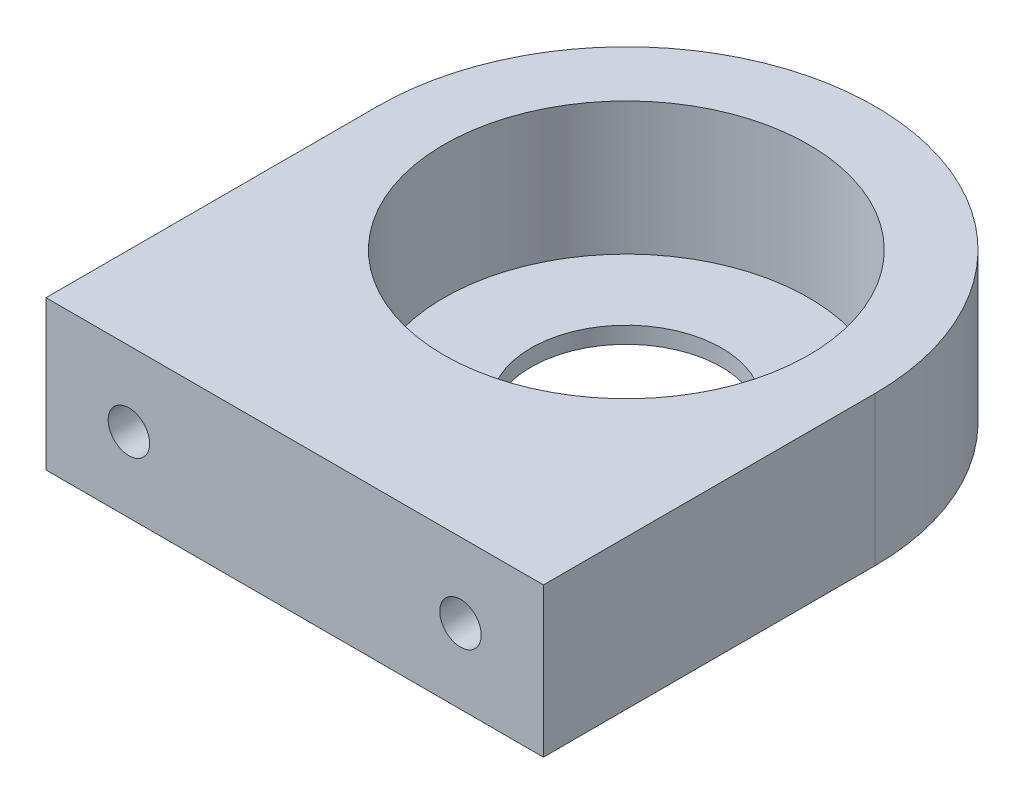
SolidWorks part; units mm, degrees
ref_plane "Front Plane" through (0, 0, 0) normal (0, 0, 1) x (1, 0, 0)
ref_plane "Top Plane" through (0, 0, 0) normal (0, 1, 0) x (1, 0, 0)
ref_plane "Right Plane" through (0, 0, 0) normal (1, 0, 0) x (0, 0, -1)
sketch "Sketch1" plane through (0, 0, 0) normal (0, 1, 0) x (1, 0, 0)
  line L0 (30, 0) -> (0, 0)
  line L1 (0, 0) -> (0, 20)
  line L2 (30, 0) -> (30, 20)
  arc A0 (30, 20) -> (0, 20) centre (15, 20) ccw
  circle A1 centre (15, 20) radius 11
  circle A2 centre (15, 20) radius 5.75
  dimension "D1" = 30
  dimension "D3" = 22
  dimension "D4" = 11.5
  dimension "D2" = 20
extrude "Boss-Extrude1" add sketch "Sketch1" along normal blind 9 contours L2 A0 L1 L0 A1 | A1 A2 region at (15, 0, -0.461) region at (4.3111, 0, -20)
sketch "Sketch2" plane through (0, 9, 0) normal (0, 1, 0) x (1, 0, 0)
  circle A0 centre (15, 20) radius 11
  circle A1 centre (15, 20) radius 5.75 construction
  dimension "D1" = 22
extrude "Cut-Extrude1" cut sketch "Sketch2" against normal blind 8
sketch "Sketch8" plane through (0, 0, 0) normal (0, 0, 1) x (1, 0, 0)
  line L0 (15, 9) -> (15, 0) construction
  line L1 (30, 9) -> (0, 9) construction
  line L2 (30, 0) -> (0, 0) construction
  line L3 (15, 0) -> (15, 4.5) construction
  line L5 (0, 9) -> (0, 0) construction
  line L7 (30, 9) -> (30, 0) construction
  line L8 (5, 4.5) -> (0, 4.5) construction
  line L9 (5, 4.5) -> (0, 4.5) construction
  line L10 (25, 4.5) -> (30, 4.5) construction
  circle A0 centre (25, 4.5) radius 1.25
  circle A1 centre (5, 4.5) radius 1.25
  dimension "D1" = 2.5
  dimension "D2" = 2.5
  dimension "D3" = 20
extrude "Cut-Extrude2" cut sketch "Sketch8" against normal blind 10
